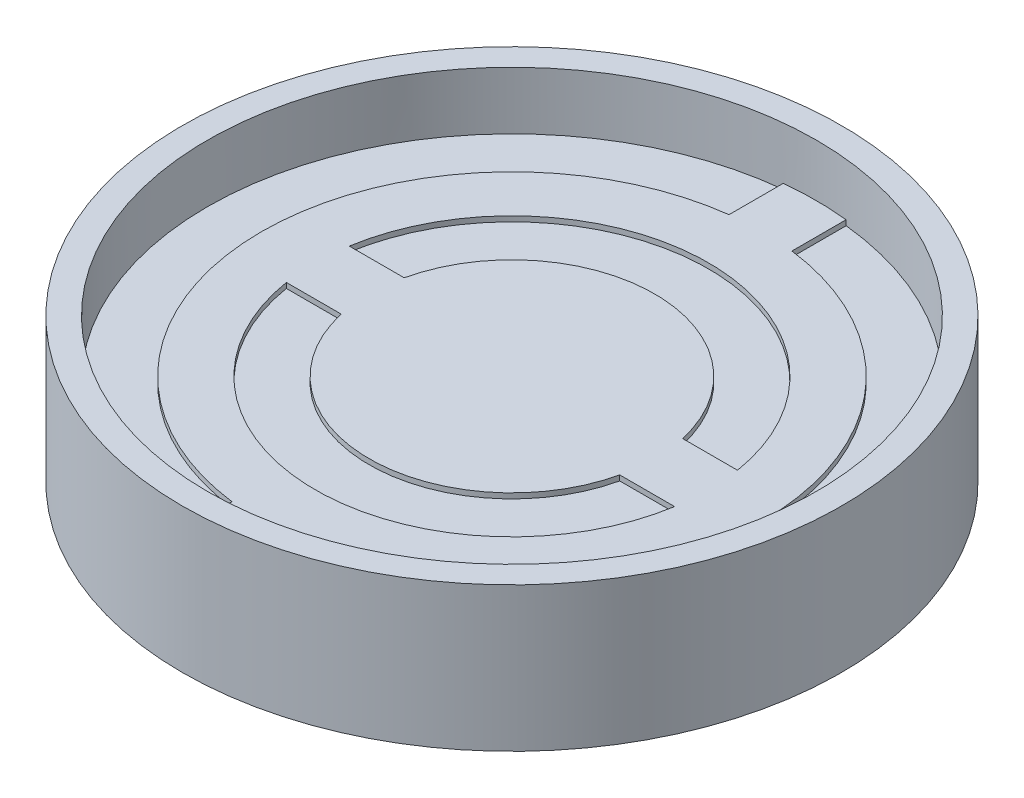
SolidWorks part; units mm, degrees
material "ABS PC"
ref_plane "Front Plane" through (0, 0, 0) normal (0, 0, 1) x (1, 0, 0)
ref_plane "Top Plane" through (0, 0, 0) normal (0, 1, 0) x (1, 0, 0)
ref_plane "Right Plane" through (0, 0, 0) normal (1, 0, 0) x (0, 0, -1)
sketch "Sketch1" plane through (0, 0, 0) normal (0, 1, 0) x (1, 0, 0)
  circle A0 centre (0, 0) radius 15.9639
  dimension "D1" = 31.9278
extrude "Boss-Extrude1" add sketch "Sketch1" along normal mid plane 6.985
sketch "Sketch2" plane through (0, 3.4925, 0) normal (0, 1, 0) x (1, 0, 0)
  circle A0 centre (0, 0) radius 14.7447
  circle A1 centre (0, 0) radius 15.9639 construction
  dimension "D1" = 1.2192
extrude "Cut-Extrude1" cut sketch "Sketch2" against normal blind 2.794
sketch "Sketch3" plane through (0, 0.6985, 0) normal (0, 1, 0) x (1, 0, 0)
  line L0 (6.9152, 0) -> (9.525, 0) construction
  line L1 (9.525, 0) -> (12.1348, 0) construction
  line L2 (12.1348, 0) -> (14.7447, 0) construction
  line L3 (-1.524, -12.0388) -> (1.524, -15.891) construction
  line L4 (-1.524, 15.891) -> (1.524, 15.891)
  line L5 (-1.524, 15.891) -> (-1.524, 12.0388)
  line L6 (-1.524, 12.0388) -> (1.524, 12.0388)
  line L7 (1.524, 15.891) -> (1.524, 12.0388)
  line L8 (-1.524, 15.891) -> (1.524, 12.0388) construction
  line L9 (-1.524, 12.0388) -> (1.524, 15.891) construction
  line L10 (-12.0388, 1.524) -> (-6.7451, 1.524)
  line L11 (-12.0388, 1.524) -> (-12.0388, -1.524)
  line L12 (-12.0388, -1.524) -> (-6.7451, -1.524)
  line L13 (-6.7451, 1.524) -> (-6.7451, -1.524)
  line L14 (-12.0388, 1.524) -> (-6.7451, -1.524) construction
  line L15 (-12.0388, -1.524) -> (-6.7451, 1.524) construction
  line L16 (-1.524, -15.891) -> (1.524, -12.0388) construction
  line L17 (1.524, -15.891) -> (1.524, -12.0388)
  line L18 (-1.524, -12.0388) -> (1.524, -12.0388)
  line L19 (-1.524, -15.891) -> (-1.524, -12.0388)
  line L20 (-1.524, -15.891) -> (1.524, -15.891)
  line L21 (0, 0) -> (0, 6.9152) construction
  line L22 (12.0388, -1.524) -> (6.7451, 1.524) construction
  line L23 (12.0388, 1.524) -> (6.7451, -1.524) construction
  line L24 (6.7451, 1.524) -> (6.7451, -1.524)
  line L25 (12.0388, -1.524) -> (6.7451, -1.524)
  line L26 (12.0388, 1.524) -> (12.0388, -1.524)
  line L27 (12.0388, 1.524) -> (6.7451, 1.524)
  circle A0 centre (0, 0) radius 6.9152
  circle A1 centre (0, 0) radius 9.525
  circle A2 centre (0, 0) radius 12.1348
  circle A3 centre (0, 0) radius 14.7447 construction
  circle A5 centre (0, 0) radius 15.9639 construction
  point P7 (0, 13.9649)
  point P17 (-9.3919, 0)
  point P28 (0, -13.9649)
  point P34 (9.3919, 0)
  circle M4 centre (0, 0) radius 14.7447
  dimension "D1" = 13.8303
  dimension "D2" = 19.05
  dimension "D3" = 24.2697
  dimension "D4" = 3.048
extrude "Boss-Extrude2" add sketch "Sketch3" along normal blind 0.254 contours L24 A0 L13 | L18 A2 L25 A1 L12 | L27 A2 L6 L10 A1 | A2 L7 L5 M4 | L10 A1 L12 A0 | L25 A1 L27 A0 | A2 L19 L17 M4 | A1 L10 L11 L12 | A1 L25 L26 L27 | L26 A2 | L24 A0 | L13 A0 | L11 A2 | L18 A2 | L6 A2 region at (0, 0.6985, -13.4106) region at (0, 0.6985, -12.0772) region at (0, 0.6985, -11.776) region at (0, 0.6985, 13.4106) region at (-10.7612, 0.6985, 0) region at (-12.0772, 0.6985, 0) region at (-8.3949, 0.6985, 8.3949) region at (0, 0.6985, 12.0772) region at (12.0772, 0.6985, 0) region at (10.7612, 0.6985, 0) region at (-8.1712, 0.6985, 0) region at (8.1712, 0.6985, 0) region at (0, 0.6985, 0) region at (-6.8132, 0.6985, 0) region at (6.8132, 0.6985, 0)
mirror "Mirror1" about plane through (0, 0, 0) normal (0, 1, 0) of "Boss-Extrude2", "Cut-Extrude1"
